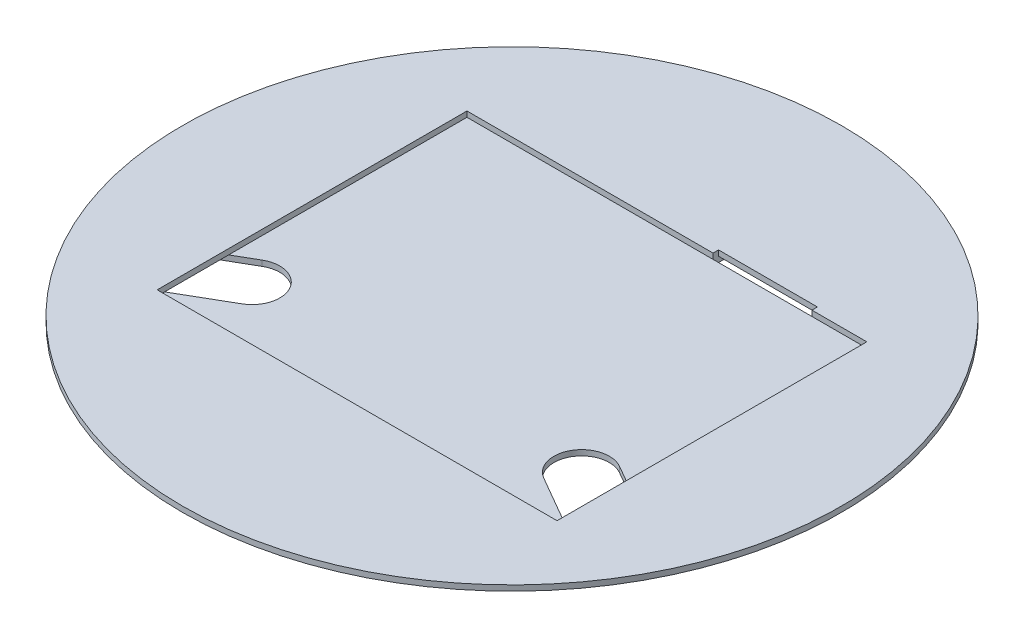
SolidWorks part; units mm, degrees
ref_plane "Front Plane" through (0, 0, 0) normal (0, 0, 1) x (1, 0, 0)
ref_plane "Top Plane" through (0, 0, 0) normal (0, 1, 0) x (1, 0, 0)
ref_plane "Right Plane" through (0, 0, 0) normal (1, 0, 0) x (0, 0, -1)
sketch "Sketch1" plane through (0, 0, 0) normal (0, 1, 0) x (1, 0, 0)
  circle A0 centre (0, 0) radius 150
  dimension "D1" = 300
extrude "Boss-Extrude1" add sketch "Sketch1" along normal blind 5
sketch "Sketch4" plane through (0, 5, 0) normal (0, 1, 0) x (1, 0, 0)
  line L1 (-91, -70.5) -> (91, -70.5)
  line L2 (-91, -70.5) -> (-91, 70.5)
  line L3 (-91, 70.5) -> (91, 70.5)
  line L4 (91, -70.5) -> (91, 70.5)
  line L5 (-91, -70.5) -> (91, 70.5) construction
  line L6 (-91, 70.5) -> (91, -70.5) construction
  point P0 (0, 0)
  dimension "D1" = 182
  dimension "D2" = 141
extrude "Cut-Extrude2" cut sketch "Sketch4" against normal blind 2.5
sketch "Sketch6" plane through (0, 0, 0) normal (0, -1, 0) x (-1, 0, 0)
  line L0 (-12.625, 86.6004) -> (-12.6304, 118.7171)
  line L1 (-109.1273, -48.4203) -> (-81.3106, -32.3666)
  line L2 (-68.6856, -54.2338) -> (-96.4968, -70.2968)
  line L3 (96.4968, -70.2968) -> (68.6856, -54.2338)
  line L4 (81.3106, -32.3666) -> (109.1273, -48.4203)
  line L5 (12.6304, 118.7171) -> (12.625, 86.6004)
  line L12 (-12.5, 86.6004) -> (-12.5054, 118.7171) construction
  line L13 (12.5054, 118.7171) -> (12.5, 86.6004) construction
  line L14 (81.2482, -32.4749) -> (109.0648, -48.5285) construction
  line L15 (96.5593, -70.1886) -> (68.7482, -54.1255) construction
  line L16 (-68.7482, -54.1255) -> (-96.5593, -70.1886) construction
  line L17 (-109.0648, -48.5285) -> (-81.2482, -32.4749) construction
  arc A0 (-12.6304, 118.7171) -> (-18.2166, 123.5391) centre (-17.5054, 118.7163) ccw
  arc A1 (-18.2166, 123.5391) -> (-116.0963, -45.9935) centre (0, 0) ccw
  circle A2 centre (0, 0) radius 150
  arc A3 (-116.0963, -45.9935) -> (-109.1273, -48.4203) centre (-111.5641, -44.198) ccw
  arc A4 (-68.6856, -54.2338) -> (-81.3106, -32.3666) centre (-75, -43.3013) ccw
  arc A5 (-96.4968, -70.2968) -> (-97.8797, -77.5456) centre (-94.0586, -74.5183) ccw
  arc A6 (-97.8797, -77.5456) -> (97.8797, -77.5456) centre (0, 0) ccw
  arc A7 (97.8797, -77.5456) -> (96.4968, -70.2968) centre (94.0586, -74.5183) ccw
  arc A8 (81.3106, -32.3666) -> (68.6856, -54.2338) centre (75, -43.3013) ccw
  arc A9 (109.1273, -48.4203) -> (116.0963, -45.9935) centre (111.5641, -44.198) ccw
  arc A10 (116.0963, -45.9935) -> (18.2166, 123.5391) centre (0, 0) ccw
  arc A11 (18.2166, 123.5391) -> (12.6304, 118.7171) centre (17.5054, 118.7163) ccw
  arc A12 (-12.625, 86.6004) -> (12.625, 86.6004) centre (0, 86.6025) ccw
  arc A26 (-12.5, 86.6004) -> (12.5, 86.6004) centre (0, 86.6025) ccw construction
  arc A27 (18.2348, 123.6628) -> (12.5054, 118.7171) centre (17.5054, 118.7163) ccw construction
  arc A28 (116.2126, -46.0396) -> (18.2348, 123.6628) centre (0, 0) ccw construction
  arc A29 (109.0648, -48.5285) -> (116.2126, -46.0396) centre (111.5641, -44.198) ccw construction
  arc A30 (81.2482, -32.4749) -> (68.7482, -54.1255) centre (75, -43.3013) ccw construction
  arc A31 (97.9777, -77.6232) -> (96.5593, -70.1886) centre (94.0586, -74.5183) ccw construction
  arc A32 (-97.9777, -77.6232) -> (97.9777, -77.6232) centre (0, 0) ccw construction
  arc A33 (-96.5593, -70.1886) -> (-97.9777, -77.6232) centre (-94.0586, -74.5183) ccw construction
  arc A34 (-68.7482, -54.1255) -> (-81.2482, -32.4749) centre (-75, -43.3013) ccw construction
  arc A35 (-116.2126, -46.0396) -> (-109.0648, -48.5285) centre (-111.5641, -44.198) ccw construction
  arc A36 (-18.2348, 123.6628) -> (-116.2126, -46.0396) centre (0, 0) ccw construction
  arc A37 (-12.5054, 118.7171) -> (-18.2348, 123.6628) centre (-17.5054, 118.7163) ccw construction
  dimension "D1" = 0.125
extrude "Cut-Extrude3" cut sketch "Sketch6" against normal blind 2.5
sketch "Sketch9" plane through (0, 5, 0) normal (0, 1, 0) x (1, 0, 0)
  line L0 (91, 70.5) -> (-91, 70.5) construction
  line L1 (21, 70.5) -> (66, 70.5)
  line L2 (21, 70.5) -> (21, 73)
  line L3 (21, 73) -> (66, 73)
  line L4 (66, 70.5) -> (66, 73)
  line L5 (91, -37.9586) -> (91, 70.5) construction
  line L6 (91, -70.5) -> (91, 70.5) construction
  dimension "D1" = 2.5
  dimension "D2" = 70
  dimension "D3" = 25
extrude "Cut-Extrude10" cut sketch "Sketch9" against normal blind 2.5
sketch "Sketch10" plane through (0, 0, 0) normal (0, -1, 0) x (1, 0, 0)
  line L1 (21, -70.5) -> (66, -70.5)
  line L2 (21, -70.5) -> (21, -80.5)
  line L3 (21, -80.5) -> (66, -80.5)
  line L4 (66, -70.5) -> (66, -80.5)
  line L14 (91, 37.9586) -> (81.3106, 32.3666)
  line L15 (91, -70.5) -> (91, 37.9586)
  line L16 (66, -70.5) -> (91, -70.5)
  line L17 (66, -73) -> (66, -70.5)
  line L18 (21, -73) -> (66, -73)
  line L19 (21, -70.5) -> (21, -73)
  line L20 (-91, -70.5) -> (21, -70.5)
  line L21 (-91, 37.9586) -> (-91, -70.5)
  line L22 (-81.3106, 32.3666) -> (-91, 37.9586)
  line L23 (-91, 67.122) -> (-68.6856, 54.2338)
  line L24 (-91, 70.5) -> (-91, 67.122)
  line L25 (91, 70.5) -> (-91, 70.5)
  line L26 (91, 67.122) -> (91, 70.5)
  line L27 (68.6856, 54.2338) -> (91, 67.122)
  line L28 (91, 37.9586) -> (81.3106, 32.3666) construction
  line L29 (91, -70.5) -> (91, 37.9586) construction
  line L30 (66, -70.5) -> (91, -70.5) construction
  line L34 (-91, -70.5) -> (21, -70.5) construction
  line L35 (-91, 37.9586) -> (-91, -70.5) construction
  line L36 (-81.3106, 32.3666) -> (-91, 37.9586) construction
  line L37 (-91, 67.122) -> (-68.6856, 54.2338) construction
  line L38 (-91, 70.5) -> (-91, 67.122) construction
  line L39 (91, 70.5) -> (-91, 70.5) construction
  line L40 (91, 67.122) -> (91, 70.5) construction
  line L41 (68.6856, 54.2338) -> (91, 67.122) construction
  arc A2 (-81.3106, 32.3666) -> (-68.6856, 54.2338) centre (-75, 43.3013) ccw
  arc A3 (68.6856, 54.2338) -> (81.3106, 32.3666) centre (75, 43.3013) ccw
  arc A4 (-81.3106, 32.3666) -> (-68.6856, 54.2338) centre (-75, 43.3013) ccw construction
  arc A5 (68.6856, 54.2338) -> (81.3106, 32.3666) centre (75, 43.3013) ccw construction
  dimension "D2" = 10
  dimension "D1" = 0
extrude "Cut-Extrude11" cut sketch "Sketch10" against normal blind 2.5
